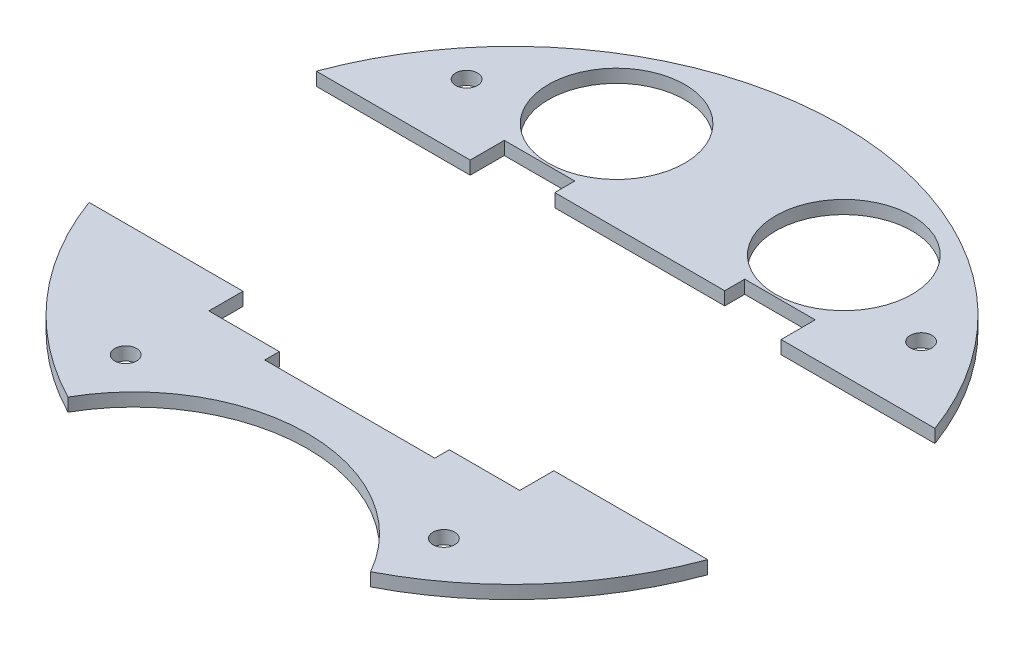
SolidWorks part; units mm, degrees
material "Acrylic (Medium-high impact)"
ref_plane "Front Plane" through (0, 0, 0) normal (0, 0, 1) x (1, 0, 0)
ref_plane "Top Plane" through (0, 0, 0) normal (0, 1, 0) x (1, 0, 0)
ref_plane "Right Plane" through (0, 0, 0) normal (1, 0, 0) x (0, 0, -1)
sketch "Sketch1" plane through (0, 0, 0) normal (0, 1, 0) x (1, 0, 0)
  line L0 (0, -83.2398) -> (-33.2911, -64.4046) construction
  line L1 (0, -83.2398) -> (0, 0) construction
  arc A0 (33.2911, -64.4046) -> (-33.2911, -64.4046) centre (0, 0) ccw
  arc A1 (33.2911, -64.4046) -> (-33.2911, -64.4046) centre (0, -83.2398) ccw
  dimension "D1" = 145
  dimension "D2" = 76.5
  dimension "D3" = 60.5
extrude "Boss-Extrude1" add sketch "Sketch1" along normal blind 2.9
sketch "solenoid placement" plane through (0, 2.9, 0) normal (0, 1, 0) x (1, 0, 0)
  line L0 (0, 0) -> (0, -36) construction
  line L1 (0, -36) -> (0, -44.9898) construction
  line L2 (-19, -36) -> (19, -36) construction
  line L3 (-19, -36) -> (-19, 28.4) construction
  line L4 (-19, 28.4) -> (19, 28.4) construction
  line L5 (19, -36) -> (19, 28.4) construction
  line L6 (-18.7, 28.1) -> (18.7, 28.1)
  line L7 (18.7, -35.7) -> (18.7, 28.1)
  line L8 (-18.7, -35.7) -> (18.7, -35.7)
  line L9 (-18.7, -35.7) -> (-18.7, 28.1)
  circle A1 centre (0, 0) radius 72.5 construction
  arc A2 (33.2911, -64.4046) -> (-33.2911, -64.4046) centre (0, 0) ccw construction
  arc A3 (33.2911, -64.4046) -> (-33.2911, -64.4046) centre (0, -83.2398) ccw construction
  dimension "D1" = 64.4
  dimension "D2" = 36
  dimension "D3" = 0.3
  dimension "D4" = 38
extrude "Cut-Extrude1" cut sketch "solenoid placement" against normal through all
sketch "Sketch7" plane through (0, 2.9, 0) normal (0, 1, 0) x (1, 0, 0)
  circle A3 centre (25, 48) radius 15
  circle A4 centre (25, 48) radius 15
  circle A5 centre (-25, 48) radius 15
  circle A6 centre (-25, 48) radius 15
  dimension "D1" = 0
  dimension "D2" = 0
extrude "Cut-Extrude6" cut sketch "Sketch7" against normal through all
sketch "Sketch8" plane through (0, 2.9, 0) normal (0, 1, 0) x (1, 0, 0)
  circle A1 centre (35, -50) radius 2.4
  circle A2 centre (35, -50) radius 2.4
  circle A3 centre (-35, -50) radius 2.4
  circle A4 centre (-35, -50) radius 2.4
  circle A5 centre (-50, 40) radius 2.4
  circle A6 centre (-50, 40) radius 2.4
  circle A7 centre (50, 40) radius 2.4
  circle A8 centre (50, 40) radius 2.4
  dimension "D1" = 0
  dimension "D2" = 0
  dimension "D3" = 0
  dimension "D4" = 0
extrude "Cut-Extrude7" cut sketch "Sketch8" against normal through all
sketch "Sketch3" plane through (0, 2.9, 0) normal (0, 1, 0) x (1, 0, 0)
  line L1 (-34.2, -32.5) -> (-22.2, -32.5)
  line L2 (-34.2, 25) -> (-68.0533, 25)
  line L3 (-34.2, 32.5) -> (-22.2, 32.5)
  line L4 (-22.2, -32.5) -> (-22.2, 32.5) construction
  line L8 (0, 0) -> (0, 72.5) construction
  line L17 (-34.2, -32.5) -> (-34.2, -25)
  line L18 (-34.2, -25) -> (-68.0533, -25)
  line L19 (-34.2, 25) -> (-34.2, 32.5)
  line L20 (-18.7, 28.1) -> (-18.7, -35.7) construction
  line L21 (-22.2, 32.5) -> (-18.7, 32.5)
  line L22 (-22.2, 32.5) -> (-22.2, -32.5) construction
  line L23 (-22.2, -32.5) -> (-18.7, -32.5)
  line L24 (-18.7, 32.5) -> (-18.7, -32.5)
  line L25 (22.2, 32.5) -> (22.2, -32.5) construction
  line L26 (22.2, -32.5) -> (22.2, 32.5) construction
  line L27 (18.7, 32.5) -> (18.7, -32.5)
  line L28 (22.2, -32.5) -> (18.7, -32.5)
  line L29 (22.2, 32.5) -> (18.7, 32.5)
  line L30 (34.2, 25) -> (34.2, 32.5)
  line L31 (34.2, -25) -> (68.0533, -25)
  line L32 (34.2, -32.5) -> (34.2, -25)
  line L33 (34.2, 32.5) -> (22.2, 32.5)
  line L34 (34.2, 25) -> (68.0533, 25)
  line L35 (34.2, -32.5) -> (22.2, -32.5)
  arc A0 (33.2911, -64.4046) -> (-33.2911, -64.4046) centre (0, 0) ccw construction
  arc A2 (68.0533, 25) -> (68.0533, -25) centre (0, 0) cw
  arc A3 (-68.0533, 25) -> (-68.0533, -25) centre (0, 0) ccw
  point P31 (-34.2, -32.5)
  dimension "D1" = 50
extrude "Cut-Extrude3" cut sketch "Sketch3" against normal through all
equation "\"smallPulleyTeeth\"= 15"
equation "\"largePulleyTeeth\"= 30"
equation "\"eighthThick\"= 2.9mm"
equation "\"sixteenthThick\" = 1.7mm"
equation "\"quarterThick\"=6.0mm"
equation "\"OD\" = 145mm"
equation "\"puckAngle\" = 60.5deg"
equation "\"D1@Sketch1\"=\"OD\""
equation "\"puckDiam\" = 76.5mm"
equation "\"D2@Sketch1\"=\"puckDiam\""
equation "\"D3@Sketch1\"=\"puckAngle\""
equation "\"D1@Boss-Extrude1\"=\"eighthThick\""
equation "\"axlePress\" = 5.9mm"
equation "\"press\" = 0.2mm"
equation "\"wheelClear\" = 0.3mm"
equation "\"10-32clear\" = 4.8mm"
equation "\"6-32clear\" = 3.3mm"
equation "\"8-32clear\" = 4.0mm"
equation "\"4-40clear\" = 3.0mm"
equation "\"wheelHeight\" = 22mm"
equation "\"wheelWell\" = 65mm"
